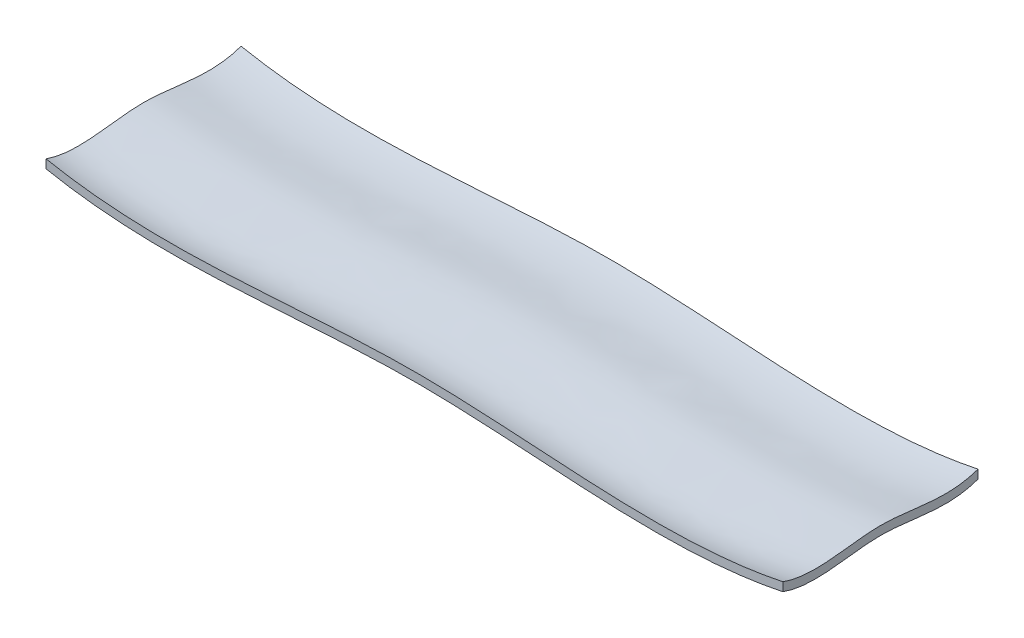
SolidWorks part; units mm, degrees
ref_plane "Front Plane" through (0, 0, 0) normal (0, 0, 1) x (1, 0, 0)
ref_plane "Top Plane" through (0, 0, 0) normal (0, 1, 0) x (1, 0, 0)
ref_plane "Right Plane" through (0, 0, 0) normal (1, 0, 0) x (0, 0, -1)
sketch "Sketch1" plane through (0, 0, 0) normal (0, 1, 0) x (1, 0, 0)
  line L5 (431.8, -114.3) -> (-431.8, -114.3)
  line L6 (431.8, -114.3) -> (431.8, 114.3)
  line L7 (431.8, 114.3) -> (-431.8, 114.3)
  line L8 (-431.8, -114.3) -> (-431.8, 114.3)
  point P0 (-431.8, 0)
  point P1 (0, 114.3)
  dimension "D1" = 863.6
  dimension "D2" = 228.6
extrude "Boss-Extrude1" add sketch "Sketch1" along normal blind 101.6
sketch "Sketch2" plane through (0, 0, 114.3) normal (0, 0, 1) x (1, 0, 0)
  line L0 (-431.8, 22.86) -> (431.8, 22.86)
  line L1 (-431.8, 101.6) -> (-431.8, 0) construction
  line L2 (431.8, 101.6) -> (431.8, 0) construction
  line L3 (-431.8, 12.7) -> (431.8, 12.7)
  line L4 (-431.8, 0) -> (431.8, 0) construction
  line L5 (-431.8, 22.86) -> (-431.8, 12.7)
  line L6 (-431.8, 17.78) -> (431.8, 17.78) construction
  line L7 (-355.6, 101.6) -> (-355.6, 0)
  line L8 (-431.8, 101.6) -> (431.8, 101.6) construction
  line L9 (330.2, 101.6) -> (330.2, 0)
  line L10 (-355.6, 22.86) -> (-431.8, 33.02)
  line L11 (-355.6, 12.7) -> (-431.8, 22.86)
  line L12 (-355.6, 17.78) -> (-431.8, 27.94) construction
  line L13 (330.2, 22.86) -> (431.8, 35.56)
  line L14 (330.2, 12.7) -> (431.8, 25.4)
  line L15 (431.8, 35.56) -> (431.8, 25.4)
  line L16 (431.8, 30.48) -> (330.2, 17.78)
  line L17 (0, 101.6) -> (0, 0)
  line L18 (0, 33.02) -> (4.2489, 33.02)
  line L19 (-431.8, 101.6) -> (-431.8, 33.02)
  line L20 (-431.8, 22.86) -> (-431.8, 33.02)
  line L23 (-431.8, 0) -> (431.8, 0)
  line L24 (431.8, 0) -> (431.8, 101.6)
  line L25 (431.8, 101.6) -> (-431.8, 101.6)
  line L26 (-431.8, 101.6) -> (-431.8, 0)
  line L27 (-431.8, 0) -> (431.8, 0)
  line L28 (431.8, 0) -> (431.8, 101.6)
  line L29 (431.8, 101.6) -> (-431.8, 101.6)
  spline S0 degree 3 poles (-431.8, 33.02) (-289.2027, 4.8776) (0.1687, 60.7689) (289.0357, 5.6648) (431.8, 35.56) knots 0 0 0 0 0.499926 1 1 1 1
  spline S1 degree 3 poles (-431.8, 22.86) (-289.2027, -5.2824) (0.1687, 50.6089) (289.0357, -4.4952) (431.8, 25.4) knots 0 0 0 0 0.499926 1 1 1 1
  dimension "D1" = 12.7
  dimension "D2" = 10.16
  dimension "D3" = 101.6
  dimension "D4" = 76.2
  dimension "D5" = 10.16
  dimension "D6" = 10.16
  dimension "D7" = 12.7
  dimension "D8" = 10.16
  dimension "D9" = 10.16
  dimension "D10" = 0
sketch "Sketch3" plane through (-431.8, 0, 0) normal (-1, 0, 0) x (0, 0, 1)
  line L0 (-57.15, 33.02) -> (-57.15, 27.94)
  line L1 (-114.3, 101.6) -> (-114.3, 0) construction
  line L2 (-114.3, 0) -> (114.3, 0) construction
  line L3 (-114.3, 33.02) -> (0, 33.02)
  line L4 (0, 33.02) -> (114.3, 33.02)
  line L5 (0, 22.86) -> (-114.3, 22.86)
  line L6 (57.15, 33.02) -> (57.15, 27.94)
  line L7 (-114.3, 33.02) -> (-114.3, 101.6)
  line L8 (0, 22.86) -> (114.3, 22.86)
  line L9 (57.15, 22.86) -> (57.15, 17.78)
  line L10 (-57.15, 22.86) -> (-57.15, 17.78)
  line L11 (-114.3, 101.6) -> (114.3, 101.6)
  line L12 (114.3, 101.6) -> (114.3, 33.02)
  line L13 (114.3, 22.86) -> (114.3, 33.02)
  line L14 (-114.3, 0) -> (114.3, 0)
  line L15 (114.3, 0) -> (114.3, 101.6)
  line L16 (114.3, 101.6) -> (-114.3, 101.6)
  line L17 (-114.3, 101.6) -> (-114.3, 0)
  line L18 (-114.3, 0) -> (114.3, 0)
  line L20 (114.3, 101.6) -> (-114.3, 101.6)
  line L22 (114.3, 22.86) -> (114.3, 0)
  line L23 (114.3, 0) -> (114.3354, -0.13)
  line L24 (114.3, 0) -> (-114.3, 0)
  line L25 (-114.3, 22.86) -> (-114.3, 0)
  line L26 (-114.3, 22.86) -> (-114.3, 33.02)
  spline S0 degree 3 poles (-114.3, 33.02) (-76.2, 19.4733) (0, 46.5667) (76.2, 19.4733) (114.3, 33.02) knots 0 0 0 0 0.5 1 1 1 1
  spline S1 degree 3 poles (-114.3, 22.86) (-76.2, 9.3133) (0, 36.4067) (76.2, 9.3133) (114.3, 22.86) knots 0 0 0 0 0.5 1 1 1 1
  point P23 (0, 0)
  dimension "D1" = 5.08
  dimension "D2" = 5.08
  dimension "D3" = 5.08
  dimension "D4" = 5.08
  dimension "D5" = 0
sweep "Cut-Sweep7" cut profiles "Sketch3" path "Sketch2"
sketch "Sketch10" plane through (-431.8, 0, 0) normal (-1, 0, 0) x (0, 0, 1)
  line L0 (114.3, 101.6) -> (114.3, 33.02) construction
  line L1 (-114.3, 101.6) -> (114.3, 101.6) construction
  line L2 (-114.3, 33.02) -> (-114.3, 101.6) construction
  line L3 (114.3, 101.6) -> (114.3, 33.02)
  line L4 (-114.3, 101.6) -> (114.3, 101.6)
  line L5 (-114.3, 33.02) -> (-114.3, 101.6)
  spline S0 degree 3 poles (-458.0318, 1995.5941) (-305.3545, -184.5161) (-0.0008, 250.555) (305.353, -184.5139) (458.0295, 1995.5609) knots -1.503639 -1.503639 -1.503639 -1.503639 0.5 2.503629 2.503629 2.503629 2.503629 only from (-114.3, 33.02) to (114.3, 33.02) construction
  spline S1 degree 3 poles (-114.3, 33.02) (-76.2, 19.4733) (0, 46.5667) (76.2, 19.4733) (114.3, 33.02) knots 0 0 0 0 0.5 1 1 1 1
sketch "Sketch11" plane through (0, 0, 114.3) normal (0, 0, 1) x (1, 0, 0)
  spline S0 degree 3 poles (-1294.0393, 1788.1894) (-906.3358, -240.1848) (-1.8263, 303.1276) (897.773, -234.0196) (1297.8214, 1790.538) knots -1.065344 -1.065344 -1.065344 -1.065344 0.499926 2.054635 2.054635 2.054635 2.054635 only from (-431.8, 33.02) to (431.8, 35.56) construction
  spline S1 degree 3 poles (-431.8, 33.02) (-289.2027, 4.8776) (0.1687, 60.7689) (289.0357, 5.6648) (431.8, 35.56) knots 0 0 0 0 0.499926 1 1 1 1
sweep "Cut-Sweep9" cut profiles "Sketch10" path "Sketch11"
sketch "Sketch12" plane through (0, 0, 0) normal (0, 1, 0) x (1, 0, 0)
  line L0 (279.4, -114.3) -> (279.4, 114.3)
  line L1 (-304.8, -114.3) -> (-304.8, 114.3)
  line L2 (431.8, -63.5) -> (279.4, -63.5)
  line L3 (-304.8, -63.5) -> (-431.8, -63.5)
  line L4 (431.8, 114.3) -> (-431.8, 114.3)
  line L5 (-431.8, 114.3) -> (-431.8, -114.3)
  line L6 (-431.8, -114.3) -> (431.8, -114.3)
  line L7 (431.8, -114.3) -> (431.8, 114.3)
  line L8 (431.8, 114.3) -> (-431.8, 114.3)
  line L9 (-431.8, 114.3) -> (-431.8, -114.3)
  line L10 (-431.8, -114.3) -> (431.8, -114.3)
  line L11 (431.8, -114.3) -> (431.8, 114.3)
  line L12 (431.8, 63.5) -> (279.4, 63.5)
  line L13 (-304.8, 63.5) -> (-431.8, 63.5)
  line L14 (431.8, -58.42) -> (279.4, -68.58)
  line L15 (0, -114.3) -> (0, 114.3)
  line L16 (279.4, 114.3) -> (-304.8, 114.3)
  line L17 (-12.7, 114.3) -> (-12.7, 101.6)
  line L18 (-12.7, -114.3) -> (-12.7, -101.6)
  line L19 (431.8, 58.42) -> (279.4, 68.58)
  line L20 (-431.8, -58.42) -> (-304.8, -68.58)
  line L21 (-431.8, 58.42) -> (-304.8, 68.58)
  line L22 (431.8, 0) -> (-431.8, 0) construction
  line L23 (419.1, -114.3) -> (419.1, 114.3)
  line L26 (-419.1, -114.3) -> (-419.1, 114.3)
  line L27 (-12.7, -101.6) -> (431.8, -101.6)
  line L28 (431.8, -101.6) -> (-431.8, -101.6)
  line L29 (-12.7, 101.6) -> (-431.8, 101.6)
  line L30 (-12.7, 101.6) -> (431.8, 101.6)
  line L33 (203.2, -114.3) -> (203.2, 114.3)
  line L34 (-228.6, -114.3) -> (-228.6, 114.3)
  arc A0 (-176.2366, 114.3) -> (-176.2366, -114.3) centre (-176.2366, 0) ccw
  arc A1 (150.8366, -114.3) -> (150.8366, 114.3) centre (150.8366, 0) ccw
  spline S0 degree 3 poles (-228.6, -101.6) (-253.0148, -91.3185) (-306.63, -48.0496) (-426.7033, -92.3384) (-433.5656, 0) (-426.7033, 92.3384) (-306.63, 48.0496) (-253.0148, 91.3185) (-228.6, 101.6) knots 0 0 0 0 0.042634 0.101499 0.132701 0.163902 0.222767 0.265401 0.265401 0.265401 0.265401
  spline S1 degree 3 poles (0, -101.8136) (-4.2316, -101.6695) (-8.4656, -101.5938) (-12.7, -101.6) knots 0.883001 0.883001 0.883001 0.883001 0.889164 0.889164 0.889164 0.889164
  spline S2 degree 3 poles (-12.7, 101.6) (-8.4656, 101.5938) (-4.2316, 101.6695) (0, 101.8136) knots 0.376237 0.376237 0.376237 0.376237 0.3824 0.3824 0.3824 0.3824
  spline S3 degree 3 poles (203.2, 101.6) (227.7092, 91.4901) (288.6458, 43.4015) (424.0867, 100.5765) (434.1303, 0) (424.0867, -100.5765) (288.6458, -43.4015) (227.7092, -91.4901) (203.2, -101.6) knots 0.487074 0.487074 0.487074 0.487074 0.529707 0.601584 0.632701 0.663817 0.735694 0.778327 0.778327 0.778327 0.778327
  point P30 (-368.3, 63.5)
  point P31 (355.6, -63.5)
  point P36 (-368.3, -63.5)
  point P37 (355.6, 63.5)
  point P38 (355.6, 63.5)
  point P39 (355.6, -63.5)
  point P40 (-368.3, 63.5)
  point P43 (-368.3, -63.5)
  dimension "D2" = 152.4
  dimension "D3" = 127
  dimension "D4" = 50.8
  dimension "D5" = 50.8
  dimension "D6" = 5.08
  dimension "D7" = 5.08
  dimension "D8" = 12.7
  dimension "D9" = 12.7
  dimension "D10" = 5.08
  dimension "D11" = 12.7
  dimension "D12" = 5.08
  dimension "D14" = 12.7
  dimension "D17" = 76.2
  dimension "D18" = 76.2
  dimension "D1" = 0
equation "\"D3@Sketch17\"=\"D2@Sketch17\""
equation "\"D4@Sketch17\"=\"D2@Sketch17\""
equation "\"D5@Sketch17\"=\"D2@Sketch17\""
equation "\"D6@Sketch17\"=\"D2@Sketch17\""
equation "\"D7@Sketch17\"=\"D2@Sketch17\""
equation "\"D8@Sketch17\"=\"D2@Sketch17\""
equation "\"D9@Sketch17\"=\"D2@Sketch17\""
